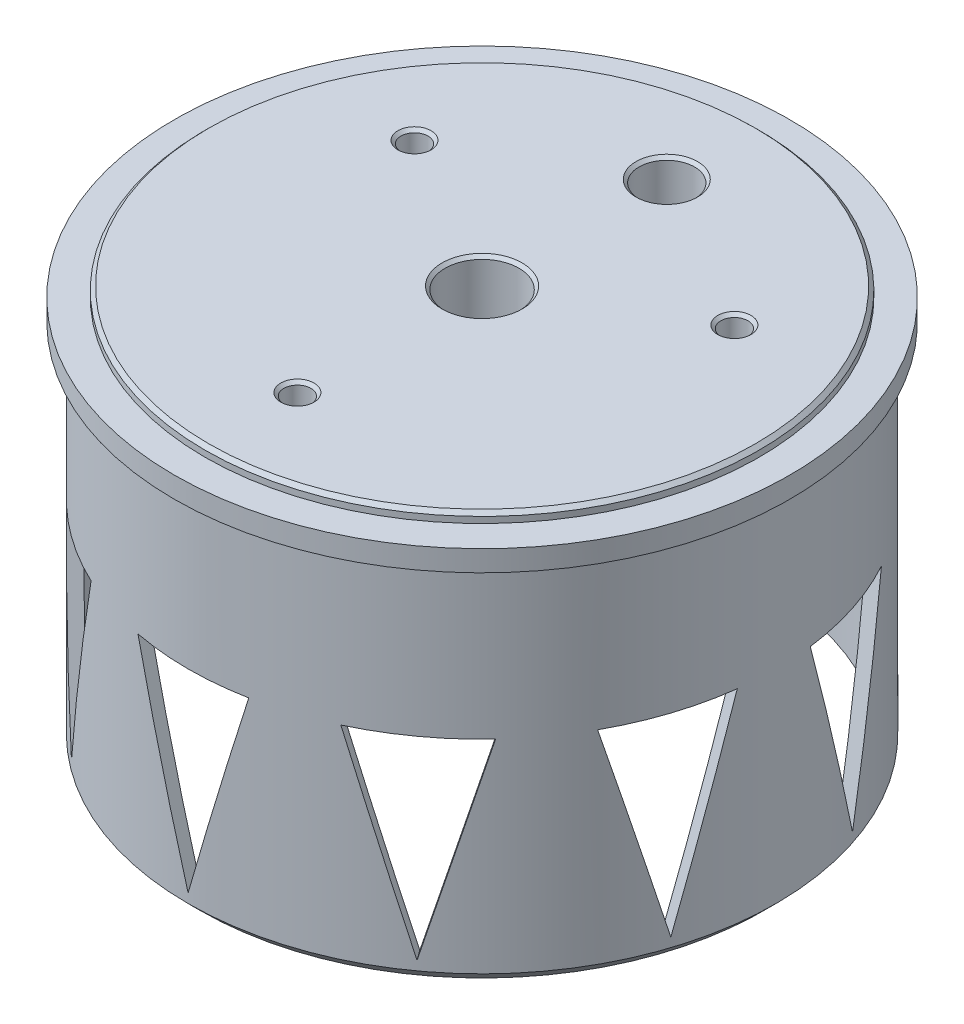
SolidWorks part; units mm, degrees
material "ABS"
ref_plane "Спереди" through (0, 0, 0) normal (0, 0, 1) x (1, 0, 0)
ref_plane "Сверху" through (0, 0, 0) normal (0, 1, 0) x (1, 0, 0)
ref_plane "Справа" through (0, 0, 0) normal (1, 0, 0) x (0, 0, -1)
sketch "Эскиз2" plane through (0, 0, 0) normal (0, 0, 1) x (1, 0, 0)
  line L0 (0, 0) -> (0, 74.988) construction
  line L1 (0, 0) -> (-47.75, 0)
  line L2 (-47.75, 0) -> (-47.75, -60)
  line L3 (-47.75, -60) -> (-45.75, -60)
  line L4 (-45.75, -60) -> (-45.75, -21)
  line L5 (-42.75, -18) -> (0, -18)
  line L6 (0, -18) -> (0, 0)
  arc A0 (-45.75, -21) -> (-42.75, -18) centre (-42.75, -21) cw
  dimension "D5" = 3
  dimension "D1" = 47.75
  dimension "D2" = 60
  dimension "D3" = 2
  dimension "D4" = 18
revolve "Основа" add sketch "Эскиз2" angle 360 about L0
sketch "Эскиз4" plane through (0, 0, 0) normal (0, 0, 1) x (1, 0, 0)
  line L0 (0, 0) -> (0, -40.75) construction
  line L1 (-9, -56.5) -> (9, -56.5) construction
  line L2 (-9, -56.5) -> (-9, -25) construction
  line L3 (-9, -25) -> (9, -25)
  line L4 (9, -56.5) -> (9, -25) construction
  line L5 (-9, -56.5) -> (9, -25) construction
  line L6 (-9, -25) -> (9, -56.5) construction
  line L8 (-9, -25) -> (0, -56.5)
  line L9 (0, -56.5) -> (9, -25)
  line L10 (-42.75, -18) -> (42.75, -18) construction
  line L11 (-42.75, -18) -> (42.75, -18)
  line L12 (-45.75, -60) -> (45.75, -60) construction
  line L13 (-45.75, -60) -> (45.75, -60)
  point P0 (0, -40.75)
  dimension "D1" = 7
  dimension "D2" = 18
  dimension "D3" = 7
  dimension "D4" = 31.891
  dimension "D6" = 74.055
extrude "Вырез облегчение" cut sketch "Эскиз4" against normal mid plane 141.7 contours L8 L9 L3 region at (0, -35.5, 0)
pattern_circular "Массив вырезов" count 5 over 360 about axis through (0, 0, 0) along (0, -1, 0) of "Вырез облегчение"
sketch "Эскиз7" plane through (0, 0, 0) normal (0, 1, 0) x (1, 0, 0)
  circle A0 centre (0, 0) radius 50
  dimension "D1" = 100
extrude "Бобышка-Вытянуть1" add sketch "Эскиз7" along normal blind 5
sketch "Эскиз8" plane through (0, 5, 0) normal (0, 1, 0) x (1, 0, 0)
  circle A0 centre (0, 0) radius 45
  circle A1 centre (0, 0) radius 50 construction
  circle A2 centre (0, 0) radius 50
  dimension "D1" = 90
extrude "Вырез-Вытянуть1" cut sketch "Эскиз8" against normal blind 1.6
sketch "Эскиз9" plane through (0, 5, 0) normal (0, 1, 0) x (1, 0, 0)
  circle A0 centre (0, 0) radius 6
  dimension "D1" = 12
extrude "Вырез-Вытянуть2" cut sketch "Эскиз9" against normal through all
sketch "Эскиз10" plane through (0, 5, 0) normal (0, 1, 0) x (1, 0, 0)
  circle A0 centre (0, 30) radius 4.5
  circle A1 centre (0, -30) radius 2.2
  circle A2 centre (25.9808, -15) radius 4.5
  circle A3 centre (-25.9808, 15) radius 2.2
  circle A4 centre (-25.9808, -15) radius 4.5
  circle A5 centre (25.9808, 15) radius 2.2
  point P15 (0, 0)
  dimension "D1" = 9
  dimension "D3" = 4.4
  dimension "D2" = 30
  dimension "D4" = 30
  dimension "D5" = 3
extrude "Вырез-Вытянуть4" cut sketch "Эскиз10" against normal through all contours A0
extrude "Вырез-Вытянуть5" cut sketch "Эскиз10<4>" against normal blind 8 contours A3 | A5 | A1
sketch "Эскиз10<4>" plane through (0, 5, 0) normal (0, 1, 0) x (1, 0, 0) same geometry as "Эскиз10"
chamfer "Фаска1" distance 0.5 angle 45 4 edges at (0, 5, -25.5) (0, 5, 32.2) (25.9808, 5, -12.8) (-25.9808, 5, -12.8)
chamfer "Фаска2" distance 0.5 angle 45 1 edges at (0, 5, 6)
chamfer "Фаска3" distance 5 angle 45 2 edges at (0, -18, 6) (0, -18, -25.5)
sketch "Эскиз13" plane through (0, 0, 0) normal (0, -1, 0) x (1, 0, 0)
  line L0 (0, 0) -> (0, -50) construction
  line L1 (-1.91, -47.7118) -> (-2, -49.96)
  line L2 (1.91, -47.7118) -> (2, -49.96)
  circle A0 centre (0, 0) radius 50 construction
  arc A1 (-2, -49.96) -> (2, -49.96) centre (0, 0) ccw
  arc A2 (-1.91, -47.7118) -> (1.91, -47.7118) centre (0, 0) ccw
  circle A3 centre (0, 0) radius 47.75 construction
  circle A4 centre (0, 0) radius 47.75 construction
  dimension "D1" = 4
extrude "Бобышка-Вытянуть2" add sketch "Эскиз13" along normal blind 7
chamfer "Фаска4" distance 1 angle 45 2 edges at (-1.955, -7, -48.8359) (1.955, -7, -48.8359)
chamfer "Фаска5" distance 2 angle 45 1 edges at (0, -60, -47.75)
chamfer "Фаска6" distance 0.6 angle 45 1 edges at (0, 5, 45)
